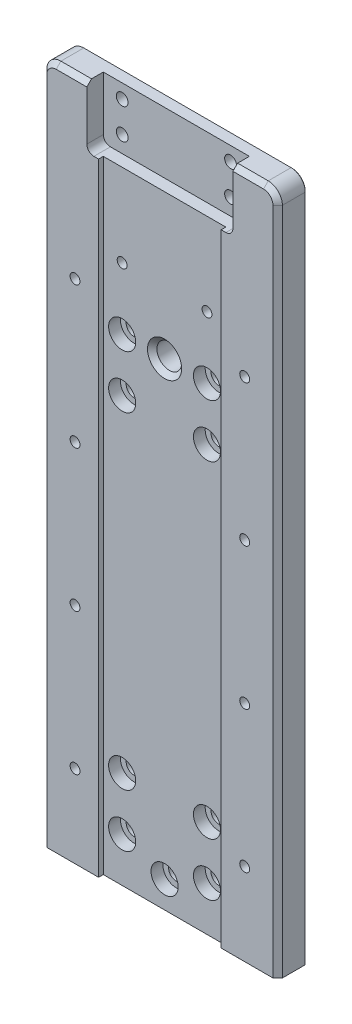
SolidWorks part; units mm, degrees
material "1060 Alloy"
ref_plane "Front Plane" through (0, 0, 0) normal (0, 0, 1) x (1, 0, 0)
ref_plane "Top Plane" through (0, 0, 0) normal (0, 1, 0) x (1, 0, 0)
ref_plane "Right Plane" through (0, 0, 0) normal (1, 0, 0) x (0, 0, -1)
sketch "Sketch1" plane through (0, 0, 0) normal (0, 0, 1) x (1, 0, 0)
  line L1 (50, -145) -> (-50, -145)
  line L2 (50, -145) -> (50, 145)
  line L3 (50, 145) -> (-50, 145)
  line L4 (-50, -145) -> (-50, 145)
  line L5 (50, -145) -> (-50, 145) construction
  line L6 (50, 145) -> (-50, -145) construction
  point P0 (0, 0)
  dimension "D1" = 100
  dimension "D2" = 290
extrude "Boss-Extrude1" add sketch "Sketch1" along normal mid plane 12
sketch "Sketch2" plane through (0, 0, 6) normal (0, 0, 1) x (1, 0, 0)
  line L0 (0, 132) -> (0, 0) construction
  line L1 (31, 119) -> (-31, 119)
  line L2 (31, 119) -> (31, 145)
  line L3 (31, 145) -> (-31, 145)
  line L4 (-31, 119) -> (-31, 145)
  line L5 (31, 119) -> (-31, 145) construction
  line L6 (31, 145) -> (-31, 119) construction
  line L7 (50, 145) -> (-50, 145) construction
  point P0 (0, 132)
  dimension "D1" = 62
  dimension "D2" = 26
extrude "Cut-Extrude1" cut sketch "Sketch2" against normal blind 7
sketch "Sketch3" plane through (0, 0, 6) normal (0, 0, 1) x (1, 0, 0)
  line L0 (-50, -145) -> (50, -145) construction
  line L1 (26, 145) -> (-26, 145)
  line L2 (26, 145) -> (26, -145)
  line L3 (26, -145) -> (-26, -145)
  line L4 (-26, 145) -> (-26, -145)
  line L5 (26, 145) -> (-26, -145) construction
  line L6 (26, -145) -> (-26, 145) construction
  point P0 (0, 0)
  dimension "D1" = 52
extrude "Cut-Extrude2" cut sketch "Sketch3" against normal blind 2
sketch "Sketch4" plane through (0, 0, -6) normal (0, 0, 1) x (1, 0, 0)
  line L0 (0, 132.5) -> (0, 0) construction
  line L1 (23, 126) -> (-23, 126) construction
  line L2 (23, 126) -> (23, 139) construction
  line L3 (23, 139) -> (-23, 139) construction
  line L4 (-23, 126) -> (-23, 139) construction
  line L5 (23, 126) -> (-23, 139) construction
  line L6 (23, 139) -> (-23, 126) construction
  line L7 (31, 145) -> (-31, 145) construction
  line L8 (-18, 83.89) -> (-18, 35.09) construction
  line L9 (-36, 145) -> (-36, -110) construction
  line L10 (-31, 145) -> (-50, 145) construction
  line L11 (-50, -145) -> (-26, -145) construction
  line L12 (0, 0) -> (0, -145) construction
  line L13 (-26, -145) -> (26, -145) construction
  line L14 (50, 23.09) -> (-50, 23.09) construction
  line L15 (18, -103.65) -> (-18, -103.65) construction
  line L16 (18, -103.65) -> (18, -126.15) construction
  line L17 (18, -126.15) -> (-18, -126.15) construction
  line L18 (-18, -103.65) -> (-18, -126.15) construction
  line L19 (18, -103.65) -> (-18, -126.15) construction
  line L20 (18, -126.15) -> (-18, -103.65) construction
  line L21 (50, 23.09) -> (50, 73.89) construction
  line L22 (50, 73.89) -> (-50, 73.89) construction
  line L23 (-50, 23.09) -> (-50, 73.89) construction
  line L24 (50, 23.09) -> (-50, 73.89) construction
  line L25 (50, 73.89) -> (-50, 23.09) construction
  circle A0 centre (-23, 139) radius 2.5
  circle A1 centre (23, 139) radius 2.5
  circle A2 centre (23, 126) radius 2.5
  circle A3 centre (-23, 126) radius 2.5
  circle A4 centre (0, 57.59) radius 5.25
  circle A5 centre (-18, 83.89) radius 2.1
  circle A6 centre (-18, 57.59) radius 3.3
  circle A7 centre (-18, 35.09) radius 3.3
  circle A9 centre (-36, 70) radius 2.1
  circle A10 centre (-36, 58.75) radius 2.1 construction
  circle A11 centre (-36, 10) radius 2.1
  circle A12 centre (-36, -110) radius 2.1
  circle A13 centre (-36, -50) radius 2.1
  circle A14 centre (-18, -103.65) radius 3.3
  circle A15 centre (-18, -126.15) radius 3.3
  circle A16 centre (18, -103.65) radius 3.3
  circle A17 centre (18, -126.15) radius 3.3
  circle A18 centre (0, -133.65) radius 3.3
  circle A20 centre (36, 70) radius 2.1
  circle A21 centre (36, 58.75) radius 2.1 construction
  circle A22 centre (18, 83.89) radius 2.1
  circle A23 centre (18, 35.09) radius 3.3
  circle A24 centre (18, 57.59) radius 3.3
  circle A25 centre (36, 10) radius 2.1
  circle A26 centre (36, -50) radius 2.1
  circle A27 centre (36, -110) radius 2.1
  point P0 (0, 132.5)
  point P36 (0, -114.9)
  point P68 (0, 48.49)
  dimension "D1" = 5
  dimension "D5" = 10.5
  dimension "D12" = 4.2
  dimension "D19" = 6.6
  dimension "D9" = 6.6
  dimension "D2" = 13
  dimension "D3" = 46
  dimension "D4" = 6
  dimension "D8" = 18
  dimension "D10" = 22.5
  dimension "D11" = 36
  dimension "D13" = 35
  dimension "D14" = 60
  dimension "D15" = 60
  dimension "D16" = 48.75
  dimension "D17" = 11.25
  dimension "D20" = 11.35
  dimension "D21" = 36
  dimension "D23" = 22.5
  dimension "D24" = 100
  dimension "D25" = 50.8
  dimension "D7" = 10
  dimension "D6" = 12
  dimension "D18" = 168.09
  dimension "D22" = 7.5
extrude "Cut-Extrude HOLES" cut sketch "Sketch4" along normal blind 21
fillet "Fillet1" radius 3 2 edges at (31, 119, 2.5) (-31, 119, 2.5)
fillet "Fillet2" radius 6 2 edges at (50, 145, 0) (-50, 145, 0)
chamfer "Chamfer1" distance 2 angle 45 6 edges at (50, -3, 6) (48.2426, 143.2426, 6) (37.5, 145, 6) (-50, -3, 6) (-48.2426, 143.2426, 6) (-37.5, 145, 6)
sketch "Sketch5" plane through (0, 0, 4) normal (0, 0, 1) x (1, 0, 0)
  circle A1 centre (-18, 57.59) radius 5.75
  circle A2 centre (-18, 35.09) radius 5.75
  circle A3 centre (18, 35.09) radius 5.75
  circle A4 centre (18, 57.59) radius 5.75
  circle A6 centre (18, -103.65) radius 5.75
  circle A7 centre (-18, -103.65) radius 5.75
  circle A8 centre (-18, -126.15) radius 5.75
  circle A9 centre (0, -133.65) radius 5.75
  circle A10 centre (18, -126.15) radius 5.75
  dimension "D1" = 11.5
extrude "Cut-Extrude5" cut sketch "Sketch5" against normal blind 5
chamfer "Chamfer2" distance 2 angle 45 1 edges at (-5.25, 57.59, 4)
chamfer "Chamfer3" distance 0.3 angle 45 5 edges at (-50, -3, -6) (-48.2426, 143.2426, -6) (48.2426, 143.2426, -6) (50, -3, -6) (0, 145, -6)
equation "\"M5_tap\"=4.2mm       ' Below you can do mesurements as follows: cm, mm, ft, in, m, "
equation "\"M5_clearence\"=5.5mm"
equation "\"M6_tap\"=5mm"
equation "\"M6_clearence\"=6.6mm"
equation "\"D1@Sketch4\"=\"M6_tap\""
equation "\"D12@Sketch4\"=\"M5_tap\""
equation "\"D19@Sketch4\"=\"M6_clearence\""
equation "\"work_area_width\"=1100mm"
equation "\"work_area_depth\"=900mm"
equation "\"steel_base_width\"=3in "
equation "\"steel_base_height\"=2in"
equation "\"steel_base_wall_thickness\"=0.125in"
equation "\"steel_base_radius\"=6mm"
equation "\"steel_sides_width\"=3in     'this tube is rotated so flip width/height"
equation "\"steel_sides_height\"=2in    'this tube is rotated so flip width/height"
equation "\"steel_sides_wall_thickness\"=0.125in"
equation "\"steel_sides_radius\"=6mm"
equation "\"steel_gantry_width\"=4in    'this tube is rotated so flip width/height"
equation "\"steel_gantry_height\"=3in    'this tube is rotated so flip width/height"
equation "\"steel_gantry_wall_thickness\"=0.125in"
equation "\"steel_gantry_radius\"=6mm"
equation "\"steel_rollers_width\"=3in"
equation "\"steel_rollers_height\"=2in    'keep as low as possible as this increases how big plastic parts are"
equation "\"steel_rollers_wall_thickness\"=0.125in"
equation "\"steel_rollers_radius\"=6mm"
equation "\"steel_zbox_width\"=4in     'if the gantry height (rotated) is too thick, a wider zbox is necessary"
equation "\"steel_zbox_height\"=2in     'hole patteren changes as the zbox and gantry height (rotated) changes."
equation "\"steel_zbox_wall_thickness\"=0.125in"
equation "\"steel_zbox_radius\"=6mm"
equation "\"alu_zangle_width\"=3.5in     'check that it doesn't interfer with the gantry"
equation "\"alu_zangle_height\"=2in"
equation "\"alu_zangle_wall_thickness\"=0.25in   'check that it doesn't interfer with the gantry"
equation "\"D9@Sketch4\"=\"M6_clearence\""
equation "\"D25@Sketch4\"=\"steel_zbox_height\""
equation "\"D6@Sketch4\"=\"steel_zbox_radius\"*2"
equation "\"D18@Sketch4\"=\"steel_gantry_width\" + \"alu_zangle_wall_thickness\" + 60.14"
equation "\"D20@Sketch4\"=\"alu_zangle_wall_thickness\" + 5"
